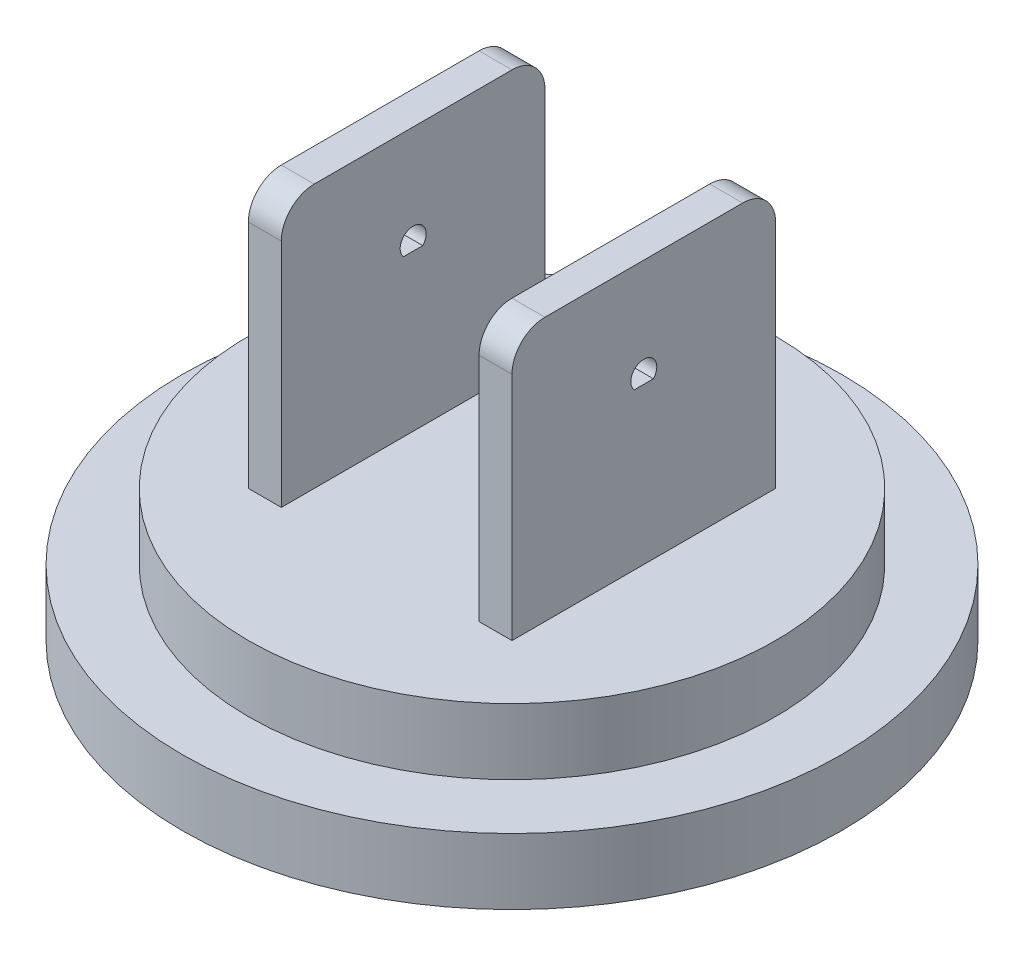
SolidWorks part; units mm, degrees
material "Plain Carbon Steel"
ref_plane "Front Plane" through (0, 0, 0) normal (0, 0, 1) x (1, 0, 0)
ref_plane "Top Plane" through (0, 0, 0) normal (0, 1, 0) x (1, 0, 0)
ref_plane "Right Plane" through (0, 0, 0) normal (1, 0, 0) x (0, 0, -1)
sketch "Sketch2" plane through (0, 0, 0) normal (0, 1, 0) x (1, 0, 0)
  circle A1 centre (0, 0) radius 63.5
  dimension "D2" = 127
extrude "Boss-Extrude1" add sketch "Sketch2" along normal blind 12.7
sketch "Sketch3" plane through (0, 12.7, 0) normal (0, 1, 0) x (1, 0, 0)
  circle A0 centre (0, 0) radius 50.8
  dimension "D1" = 101.6
extrude "Boss-Extrude2" add sketch "Sketch3" along normal blind 12.7
sketch "Sketch4" plane through (0, 0, 0) normal (0, -1, 0) x (1, 0, 0)
  circle A0 centre (0, 0) radius 6.35
  dimension "D1" = 12.7
extrude "Boss-Extrude3" add sketch "Sketch4" along normal blind 25.4
sketch "Sketch5" plane through (0, 25.4, 0) normal (0, 1, 0) x (1, 0, 0)
  line L0 (0, 0) -> (0, 17.7689) construction
  line L1 (25.4, -25.4) -> (19.05, -25.4)
  line L2 (-25.4, 25.4) -> (-19.05, 25.4)
  line L3 (-25.4, 25.4) -> (-25.4, -25.4)
  line L4 (-25.4, -25.4) -> (-19.05, -25.4)
  line L5 (-19.05, 25.4) -> (-19.05, -25.4)
  line L6 (19.05, 25.4) -> (19.05, -25.4)
  line L7 (25.4, 25.4) -> (19.05, 25.4)
  line L8 (25.4, 25.4) -> (25.4, -25.4)
  dimension "D1" = 6.35
  dimension "D2" = 50.8
  dimension "D3" = 25.4
  dimension "D4" = 19.05
extrude "Boss-Extrude4" add sketch "Sketch5" along normal blind 50.8
fillet "Fillet1" radius 6.35 4 edges at (22.225, 76.2, 25.4) (-22.225, 76.2, 25.4) (22.225, 76.2, -25.4) (-22.225, 76.2, -25.4)
sketch "Sketch6" plane through (-25.4, 0, 0) normal (-1, 0, 0) x (0, 0, 1)
  line L0 (-19.05, 76.2) -> (19.05, 76.2) construction
  line L1 (25.4, 69.85) -> (25.4, 25.4) construction
  line L2 (-1.8555, 55.4717) -> (1.8555, 55.4717)
  arc A0 (1.8555, 55.4717) -> (-1.8555, 55.4717) centre (0, 57.15) ccw
  dimension "D1" = 5.0038
  dimension "D2" = 19.05
  dimension "D3" = 25.4
  dimension "D4" = 3.711
extrude "Cut-Extrude1" cut sketch "Sketch6" against normal through all
sketch "Sketch7" plane through (0, -25.4, 0) normal (0, -1, 0) x (1, 0, 0)
  line L7 (0, 0) -> (0, 6.35) construction
  line L8 (0, 5.08) -> (0.7102, 6.3102)
  line L9 (0, 5.08) -> (-0.7102, 6.3102)
  arc A6 (0.7102, 6.3102) -> (-0.7102, 6.3102) centre (0, 0) ccw
  dimension "D1" = 30
  dimension "D2" = 6.35
  dimension "D3" = 1.4205
  dimension "D4" = 1.4205
extrude "Cut-Extrude2" cut sketch "Sketch7" against normal blind 12.7
pattern_circular "CirPattern1" count 28 over 360 about axis through (0, -25.4, 0) along (0, 1, 0) of "Cut-Extrude2" reverse direction yes
